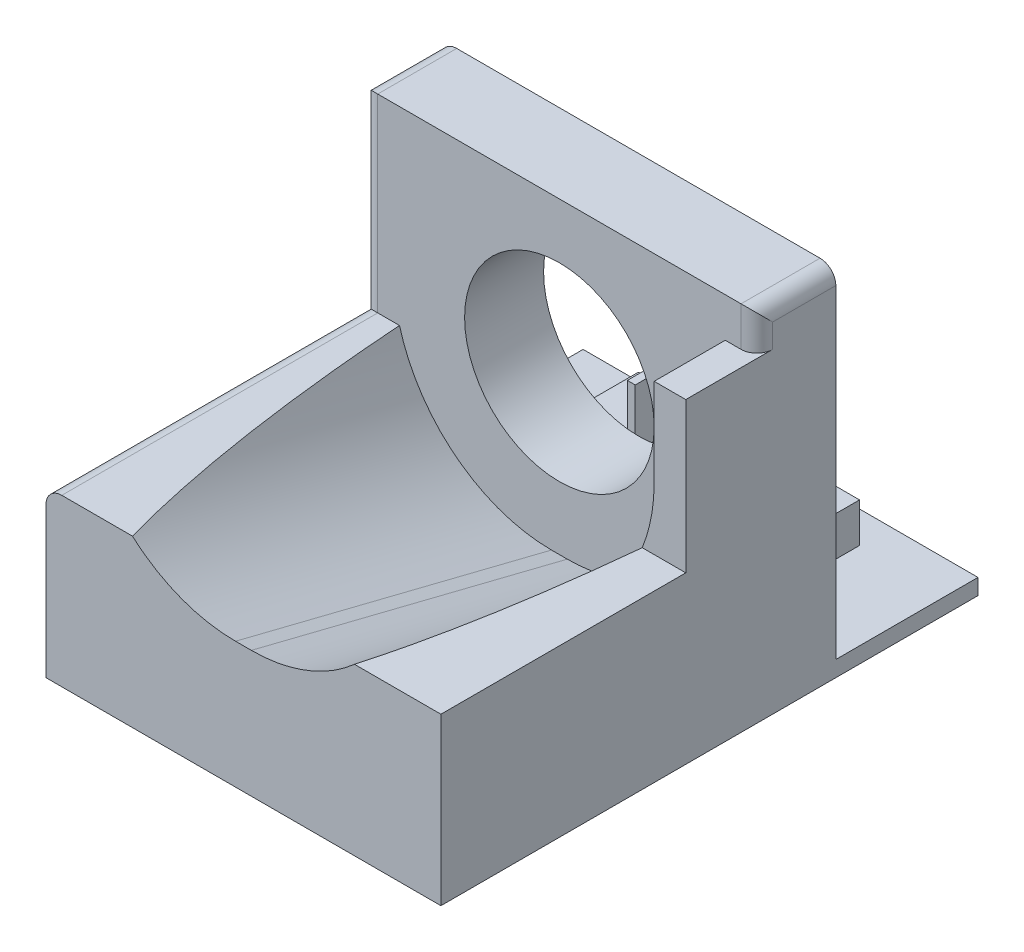
SolidWorks part; units mm, degrees
ref_plane "Front Plane" through (0, 0, 0) normal (0, 0, 1) x (1, 0, 0)
ref_plane "Top Plane" through (0, 0, 0) normal (0, 1, 0) x (1, 0, 0)
ref_plane "Right Plane" through (0, 0, 0) normal (1, 0, 0) x (0, 0, -1)
sketch "Sketch2" plane through (0, 0, 0) normal (0, 1, 0) x (1, 0, 0)
  line L1 (-125, 125) -> (125, 125)
  line L2 (-125, 125) -> (-125, -125)
  line L3 (-125, -125) -> (125, -125)
  line L4 (125, 125) -> (125, -125)
  line L5 (-125, 125) -> (125, -125) construction
  line L6 (-125, -125) -> (125, 125) construction
  point P0 (0, 0)
  dimension "D1" = 250
  dimension "D2" = 250
extrude "Boss-Extrude1" add sketch "Sketch2" along normal blind 250
sketch "Sketch3" plane through (0, 250, 0) normal (0, 1, 0) x (1, 0, 0)
  line L0 (-105, -125) -> (-105, 75)
  line L1 (-125, -125) -> (125, -125) construction
  line L2 (-105, 75) -> (105, 75)
  line L3 (105, 75) -> (105, -125)
  line L4 (105, -125) -> (-105, -125)
  line L5 (-125, 125) -> (-125, -125) construction
  line L6 (125, -125) -> (125, 125) construction
  dimension "D1" = 200
  dimension "D2" = 20
  dimension "D3" = 20
extrude "Cut-Extrude1" cut sketch "Sketch3" against normal blind 220
sketch "Sketch5" plane through (105, 0, 0) normal (-1, 0, 0) x (0, 0, 1)
  line L0 (125, 30) -> (125, 80)
  line L1 (125, 250) -> (125, 0) construction
  line L2 (125, 80) -> (-75, 30)
  line L3 (-75, 30) -> (125, 30)
  line L4 (-125, 0) -> (125, 0) construction
  dimension "D1" = 50
  dimension "D2" = 30
  dimension "D3" = 30
extrude "Boss-Extrude2" add sketch "Sketch5" along normal through all
fillet "Fillet1" radius 100 2 edges at (105, 55, 25) (-105, 55, 25)
fillet "Fillet2" radius 20 5 edges at (0, 250, -75) (105, 250, 25) (-105, 250, 25) (115, 250, 125) (-115, 250, 125)
sketch "Sketch8" plane through (0, 0, -75) normal (0, 0, 1) x (1, 0, 0)
  line L0 (0, 230) -> (0, 30) construction
  line L1 (105, 230) -> (-105, 230) construction
  line L2 (5, 30) -> (-5, 30) construction
  circle A0 centre (0, 130) radius 90
  circle A1 centre (0, 130) radius 40
  circle A2 centre (0, 130) radius 30
sketch "Sketch10" plane through (0, 0, -75) normal (0, 0, 1) x (1, 0, 0)
  line L0 (90.2636, 79.219) -> (2.3315, 120.2224) construction
  line L1 (5, 30) -> (-5, 30) construction
  ellipse E0 centre (5, 133.0776) end of major axis (5, 30) minor radius 100 (5, 30) -> (105, 133.0776) ccw construction
  dimension "D1" = 25
sketch "Sketch11" plane through (0, 0, -75) normal (0, 0, 1) x (1, 0, 0)
  circle A0 centre (0, 130) radius 60
  dimension "D1" = 120
extrude "Cut-Extrude2" cut sketch "Sketch11" against normal through all
sketch "Sketch12" plane through (0, 0, -125) normal (0, 0, -1) x (-1, 0, 0)
  line L0 (125, 250) -> (125, 0) construction
  line L1 (-125, 0) -> (125, 0)
  line L2 (-125, 0) -> (-125, 10)
  line L3 (-125, 10) -> (125, 10)
  line L4 (125, 0) -> (125, 10)
  dimension "D1" = 10
extrude "Boss-Extrude3" add sketch "Sketch12" along normal blind 90
sketch "Sketch13" plane through (0, 0, -125) normal (0, 0, -1) x (-1, 0, 0)
  line L0 (125, 10) -> (-125, 10) construction
  line L1 (-70, 30) -> (70, 30)
  line L2 (-70, 30) -> (-70, 35)
  line L3 (-70, 35) -> (70, 35)
  line L4 (70, 30) -> (70, 35)
  line L5 (0, -14.686) -> (0, 276.0698) construction
  line L6 (125, 10) -> (-125, 10) construction
  line L7 (70, 30) -> (65, 30)
  line L8 (70, 30) -> (70, 10)
  line L9 (70, 10) -> (65, 10)
  line L10 (65, 30) -> (65, 10)
  line L12 (-70, 30) -> (-65, 30)
  line L13 (-70, 30) -> (-70, 10)
  line L14 (-70, 10) -> (-65, 10)
  line L15 (-65, 30) -> (-65, 10)
  line M13 (-125, 10) -> (125, 10)
  dimension "D1" = 20
  dimension "D2" = 5
  dimension "D3" = 140
  dimension "D4" = 70
  dimension "D5" = 5
  dimension "D6" = 5
extrude "Boss-Extrude4" add sketch "Sketch13" along normal blind 50 from offset 20 contours L1 L5 L3 L2 | L5 L1 L4 L3 | L1 L10 L8 M13 | L15 L1 L13 M13 region at (35, 32.5, -125) region at (67.5, 20, -125) region at (-35, 32.5, -125) region at (-67.5, 20, -125)
sketch "Sketch14" plane through (0, 0, -125) normal (0, 0, -1) x (-1, 0, 0)
  line L0 (0, 272.4379) -> (0, -35.0037) construction
  line L1 (-70, 35) -> (70, 35) construction
  line L2 (22, 35) -> (27, 35)
  line L3 (22, 35) -> (22, 77)
  line L4 (22, 77) -> (27, 77)
  line L5 (27, 35) -> (27, 77)
  line L6 (-70, 35) -> (70, 35) construction
  line L7 (-22, 35) -> (-27, 35)
  line L8 (-22, 35) -> (-22, 77)
  line L9 (-22, 77) -> (-27, 77)
  line L10 (-27, 35) -> (-27, 77)
  dimension "D1" = 5
  dimension "D2" = 5
  dimension "D3" = 44
  dimension "D4" = 22
  dimension "D5" = 42
  dimension "D6" = 42
extrude "Boss-Extrude5" add sketch "Sketch14" along normal blind 50 from offset 20
sketch "Sketch15" plane through (125, 0, 0) normal (1, 0, 0) x (0, 0, -1)
  line L14 (125, 250) -> (125, 10) construction
  line L15 (44.23, 167.66) -> (64.23, 167.66)
  line L16 (44.23, 167.66) -> (44.23, 127.66)
  line L17 (44.23, 127.66) -> (64.23, 127.66)
  line L18 (64.23, 167.66) -> (64.23, 127.66)
  line L19 (-125, 0) -> (215, 0) construction
  dimension "D1" = 60.77
  dimension "D2" = 127.66
  dimension "D3" = 20
  dimension "D4" = 40
extrude "Cut-Extrude3" cut sketch "Sketch15" against normal blind 20
sketch "Sketch17" plane through (125, 0, 0) normal (1, 0, 0) x (0, 0, -1)
  line L0 (64.23, 167.66) -> (44.23, 167.66) construction
  line L1 (44.23, 162.66) -> (64.23, 162.66)
  line L2 (44.23, 162.66) -> (44.23, 122.66)
  line L3 (44.23, 122.66) -> (64.23, 122.66)
  line L4 (64.23, 162.66) -> (64.23, 122.66)
  line L5 (44.23, 167.66) -> (44.23, 127.66) construction
  dimension "D1" = 20
  dimension "D2" = 40
  dimension "D3" = 5
extrude "Cut-Extrude5" cut sketch "Sketch17" against normal blind 23
sketch "Sketch18" plane through (125, 0, 0) normal (1, 0, 0) x (0, 0, -1)
  line L0 (64.23, 122.66) -> (64.23, 167.66) construction
  line L1 (44.23, 167.66) -> (64.23, 167.66)
  line L2 (44.23, 167.66) -> (44.23, 157.66)
  line L3 (44.23, 157.66) -> (64.23, 157.66)
  line L4 (64.23, 167.66) -> (64.23, 157.66)
  dimension "D1" = 10
extrude "Boss-Extrude6" add sketch "Sketch18" against normal blind 20
sketch "Sketch19" plane through (-125, 0, 0) normal (-1, 0, 0) x (0, 0, 1)
  line L0 (125, 230) -> (125, 0) construction
  line L1 (-125, 250) -> (125, 250)
  line L2 (-125, 250) -> (-125, 200)
  line L3 (-125, 200) -> (125, 200)
  line L4 (125, 250) -> (125, 200)
  dimension "D1" = 50
extrude "Cut-Extrude11" cut sketch "Sketch19" against normal blind 70
sketch "Sketch24" plane through (-125, 0, 0) normal (-1, 0, 0) x (0, 0, 1)
  line L1 (125, 200) -> (-75, 200)
  line L2 (125, 200) -> (125, 105)
  line L3 (125, 105) -> (-75, 105)
  line L4 (-75, 200) -> (-75, 105)
  dimension "D1" = 95
  dimension "D2" = 200
extrude "Cut-Extrude12" cut sketch "Sketch24" against normal blind 70
sketch "Sketch25" plane through (-125, 0, 0) normal (-1, 0, 0) x (0, 0, 1)
  line L1 (125, 105) -> (-30, 105)
  line L2 (125, 105) -> (125, 250)
  line L4 (-30, 105) -> (-30, 200)
  line L5 (-75, 133.0776) -> (-75, 230) construction
  line L6 (125, 250) -> (-75, 250)
  line L8 (-30, 200) -> (-75, 200)
  line L9 (-75, 250) -> (-75, 200)
  line L10 (-75, 200) -> (-75, 230) construction
  dimension "D1" = 50
  dimension "D2" = 145
  dimension "D3" = 155
extrude "Cut-Extrude14" cut sketch "Sketch25" against normal through all
sketch "Sketch26" plane through (0, 0, -75) normal (0, 0, 1) x (1, 0, 0)
  line L1 (125, 250) -> (50, 250)
  line L2 (125, 250) -> (125, 200)
  line L3 (125, 200) -> (50, 200)
  line L4 (50, 250) -> (50, 200)
  dimension "D1" = 50
  dimension "D2" = 75
extrude "Cut-Extrude15" cut sketch "Sketch26" against normal through all
sketch "Sketch27" plane through (125, 0, 0) normal (1, 0, 0) x (0, 0, -1)
  line L0 (75, 230) -> (75, 200) construction
  line L1 (125, 200) -> (75, 200)
  line L2 (125, 200) -> (125, 225)
  line L3 (125, 225) -> (75, 225)
  line L4 (75, 200) -> (75, 225)
  dimension "D1" = 25
extrude "Boss-Extrude7" add sketch "Sketch27" against normal up to surface (250 mm away) up to face at (-125, 78.75, -72.5)
sketch "Sketch28" plane through (50, 0, 0) normal (1, 0, 0) x (0, 0, -1)
  line L1 (125, 225) -> (75, 225)
  line L2 (125, 225) -> (125, 250)
  line L3 (125, 250) -> (75, 250)
  line L4 (75, 225) -> (75, 250)
  dimension "D1" = 25
  dimension "D2" = 50
extrude "Cut-Extrude16" cut sketch "Sketch28" against normal through all both and the other way through all
fillet "Fillet3" radius 10 5 edges at (125, 212.5, -75) (-125, 165, -75) (-125, 105, 25) (125, 225, -100) (-125, 225, -100)
sketch "Sketch29" plane through (0, 200, 0) normal (0, 1, 0) x (1, 0, 0)
  line L0 (105, 75) -> (105, 64.23) construction
  line L1 (125, 30) -> (105, 30)
  line L2 (125, 30) -> (125, 69.615)
  line L3 (125, 69.615) -> (105, 69.615)
  line L4 (105, 30) -> (105, 69.615)
extrude "Boss-Extrude8" add sketch "Sketch29" against normal up to surface (95 mm away) up to face at (104.9831, 105, 49.1444)
